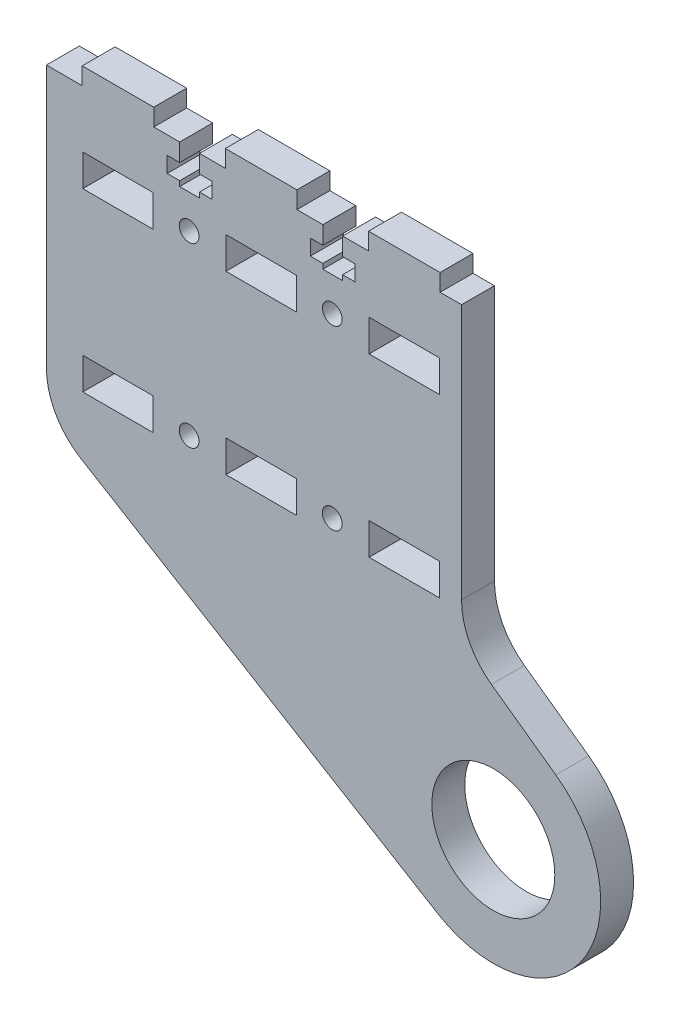
SolidWorks part; units mm, degrees
ref_plane "Front Plane" through (0, 0, 0) normal (0, 0, 1) x (1, 0, 0)
ref_plane "Top Plane" through (0, 0, 0) normal (0, 1, 0) x (1, 0, 0)
ref_plane "Right Plane" through (0, 0, 0) normal (1, 0, 0) x (0, 0, -1)
sketch "Sketch1" plane through (0, 0, 0) normal (0, 0, 1) x (1, 0, 0)
  line L0 (-38.0203, 0) -> (38.1796, 0) construction
  line L1 (31.7297, -12.8) -> (19.2297, -12.8)
  line L2 (38.1796, -12.8536) -> (38.1796, 12.8536)
  line L3 (31.7297, 12.8) -> (19.2297, 12.8)
  line L4 (-38.0203, -12.8) -> (-38.0203, 12.8)
  line L5 (38.1796, -12.8536) -> (-38.0203, 12.8) construction
  line L6 (38.1796, 12.8536) -> (-38.0203, -12.8) construction
  line L7 (6.3297, 18.442) -> (-6.1703, 18.442)
  line L8 (-19.0703, -18.442) -> (-31.5703, -12.8) construction
  line L9 (-19.0703, -12.8) -> (-31.5703, -18.442) construction
  line L10 (6.3297, -12.8) -> (-6.1703, -12.8)
  line L11 (-19.0703, -12.8) -> (-31.5703, -12.8)
  line L12 (31.7297, -12.8) -> (31.7297, -18.442)
  line L13 (19.2297, -12.8) -> (19.2297, -18.442)
  line L14 (38.1796, 28.575) -> (31.8297, 28.575)
  line L15 (-19.0703, 12.8) -> (-19.0703, 18.442)
  line L16 (-19.0703, 18.442) -> (-31.5703, 18.442)
  line L17 (-31.5703, 12.8) -> (-31.5703, 18.442)
  line L18 (-19.0703, 12.8) -> (-31.5703, 18.442) construction
  line L19 (-19.0703, 18.442) -> (-31.5703, 12.8) construction
  line L20 (-6.1703, 12.8) -> (-6.1703, 18.442)
  line L21 (6.3297, 12.8) -> (6.3297, 18.442)
  line L22 (31.7297, 18.442) -> (19.2297, 18.442)
  line L23 (19.2297, 12.8) -> (19.2297, 18.442)
  line L24 (31.7297, 12.8) -> (31.7297, 18.442)
  line L25 (-19.0703, 12.8) -> (-31.5703, 12.8)
  line L26 (6.3297, 12.8) -> (-6.1703, 12.8)
  line L27 (-38.0203, 12.8) -> (-38.0203, 28.575)
  line L28 (0.0797, 0) -> (0.0797, 28.575) construction
  line L29 (11.0271, 28.575) -> (6.4297, 28.575)
  line L30 (38.1796, 28.575) -> (38.1796, 12.8536)
  line L31 (31.7297, -18.442) -> (19.2297, -18.442)
  line L32 (6.3297, -12.8) -> (6.3297, -18.442)
  line L33 (-6.1703, -12.8) -> (-6.1703, -18.442)
  line L34 (-31.5703, -12.8) -> (-31.5703, -18.442)
  line L35 (-19.0703, -18.442) -> (-31.5703, -18.442)
  line L36 (-19.0703, -12.8) -> (-19.0703, -18.442)
  line L37 (6.3297, -18.442) -> (-6.1703, -18.442)
  line L38 (31.7297, -12.8) -> (19.2297, -12.8)
  line L39 (-19.0703, -12.8) -> (-31.5703, -12.8)
  line L40 (6.3297, -12.8) -> (-6.1703, -12.8)
  line L41 (6.3297, 12.8) -> (19.2297, 12.8) construction
  line L42 (-38.0203, -25.146) -> (31.4234, -67.1049)
  line L43 (38.1796, -25.146) -> (52.371, -35.3151)
  line L44 (-10.8677, 22.1694) -> (-14.3729, 22.1694) construction
  line L45 (-8.6516, 24.0109) -> (-16.5891, 24.0109) construction
  line L46 (-10.8677, 26.9875) -> (-14.3729, 26.9875) construction
  line L47 (-12.6203, 28.575) -> (-12.6203, 24.5335) construction
  line L48 (-6.1703, 12.8) -> (-19.0703, 12.8) construction
  line L49 (-14.3729, 21.717) -> (-14.3729, 22.6219)
  line L50 (12.7797, 0) -> (12.7797, 28.575) construction
  line L51 (14.5323, 25.4) -> (16.7484, 25.4)
  line L52 (14.5323, 22.6219) -> (16.7484, 22.6219)
  line L53 (11.0271, 25.4) -> (11.0271, 28.575)
  line L54 (-10.8677, 21.717) -> (-10.8677, 22.6219)
  line L55 (-38.0203, -12.8) -> (-38.0203, -25.146)
  line L56 (14.5323, 25.4) -> (14.5323, 28.575)
  line L57 (12.7797, 28.575) -> (12.7797, 24.5335) construction
  line L58 (38.1796, -12.8536) -> (38.1796, -25.146)
  line L59 (11.0271, 26.9875) -> (14.5323, 26.9875) construction
  line L60 (8.8109, 22.6219) -> (11.0271, 22.6219)
  line L61 (8.8109, 22.6219) -> (8.8109, 25.4)
  line L62 (8.8109, 25.4) -> (11.0271, 25.4)
  line L63 (16.7484, 22.6219) -> (16.7484, 25.4)
  line L64 (12.7797, 24.5335) -> (12.7797, 20.1202) construction
  line L65 (8.8109, 24.0109) -> (16.7484, 24.0109) construction
  line L66 (11.0271, 21.717) -> (14.5323, 21.717)
  line L67 (11.0271, 21.717) -> (11.0271, 22.6219)
  line L68 (-6.2703, 28.575) -> (-10.8677, 28.575)
  line L69 (14.5323, 21.717) -> (14.5323, 22.6219)
  line L70 (12.7797, 20.1202) -> (12.7797, 21.717) construction
  line L71 (11.0271, 22.1694) -> (14.5323, 22.1694) construction
  line L72 (-10.8677, 21.717) -> (-14.3729, 21.717)
  line L73 (-16.5891, 22.6219) -> (-16.5891, 25.4)
  line L74 (-8.6516, 25.4) -> (-10.8677, 25.4)
  line L75 (-8.6516, 22.6219) -> (-8.6516, 25.4)
  line L76 (-8.6516, 22.6219) -> (-10.8677, 22.6219)
  line L77 (-14.3729, 25.4) -> (-14.3729, 28.575)
  line L78 (-10.8677, 25.4) -> (-10.8677, 28.575)
  line L79 (-14.3729, 22.6219) -> (-16.5891, 22.6219)
  line L80 (-14.3729, 25.4) -> (-16.5891, 25.4)
  line L81 (-14.3729, 28.575) -> (-18.9703, 28.575)
  line L82 (19.1297, 31.623) -> (19.1297, 28.575)
  line L83 (-6.2703, 31.623) -> (6.4297, 31.623)
  line L84 (-6.2703, 31.623) -> (-6.2703, 28.575)
  line L85 (31.8297, 31.623) -> (31.8297, 28.575)
  line L86 (6.4297, 31.623) -> (6.4297, 28.575)
  line L87 (0.0797, 28.575) -> (0.0797, 31.623) construction
  line L88 (-6.2703, 30.099) -> (6.4297, 30.099) construction
  line L89 (31.8297, 30.099) -> (19.1297, 30.099) construction
  line L90 (31.8297, 31.623) -> (19.1297, 31.623)
  line L91 (19.1297, 28.575) -> (14.5323, 28.575)
  line L92 (-18.9703, 31.623) -> (-18.9703, 28.575)
  line L93 (-31.6703, 31.623) -> (-18.9703, 31.623)
  line L94 (-31.6703, 30.099) -> (-18.9703, 30.099) construction
  line L95 (-31.6703, 31.623) -> (-31.6703, 28.575)
  line L96 (-31.6703, 28.575) -> (-38.0203, 28.575)
  arc A0 (31.4234, -67.1049) -> (52.371, -35.3151) centre (41.275, -50.8) ccw
  circle A1 centre (12.7, 15.721) radius 1.7526
  circle A2 centre (-12.7, 15.721) radius 1.7526
  circle A3 centre (12.7, -15.721) radius 1.7526
  circle A4 centre (-12.7, -15.721) radius 1.7526
  circle A6 centre (41.275, -50.8) radius 10.9125
  point P0 (0, 0)
  point P8 (-25.3203, 15.621)
  point P16 (12.7, 30.1625)
  point P37 (-25.3203, -15.621)
  point P55 (12.7797, 26.9875)
  point P59 (12.7797, 24.0109)
  point P60 (-0.4211, 99.3522)
  point P62 (-25.6211, 23.1522)
  point P65 (12.7797, 22.1694)
  point P70 (-3.225, -28.575)
  point P73 (12.7797, 24.0109)
  point P91 (-12.6203, 24.0109)
  point P92 (-12.6203, 22.1694)
  point P97 (-12.6203, 26.9875)
  point P98 (-12.5407, 30.1625)
  point P99 (0.0797, 30.099)
  point P117 (25.4797, 30.099)
  point P120 (-25.3203, 30.099)
  dimension "D3" = 12.5
  dimension "D5" = 50.8
  dimension "D6" = 41.275
  dimension "D8" = 12.7
  dimension "D13" = 3.5052
  dimension "D11" = 28.575
  dimension "D19" = 21.825
  dimension "D7" = 38.1
  dimension "D1" = 25.6
  dimension "D2" = 76.2
  dimension "D4" = 5.642
  dimension "D9" = 12.7
  dimension "D10" = 3
  dimension "D12" = 2.921
  dimension "D14" = 2.921
  dimension "D15" = 15.721
  dimension "D16" = 12.7
  dimension "D17" = 3.048
  dimension "D20" = 9.525
  dimension "D21" = 9.525
  dimension "D18" = 12.7
  dimension "D22" = 3.5052
  dimension "D23" = 2.7781
  dimension "D24" = 7.9375
  dimension "D25" = 3.175
  dimension "D26" = 0.9049
extrude "Boss-Extrude1" add sketch "Sketch1" along normal blind 5.842 contours L58 L2 L30 L27 L4 L55 A4 L32 L37 L33 L10 L11 L36 L35 L34 L12 L31 L13 L1 L21 L26 L20 L7 L15 L25 L17 L16 L24 L3 L23 L22 region at (7.1677, -13.6845, 0)
fillet "Fillet1" [suppressed] radius 3.175
fillet "Fillet2" [suppressed] radius 3.175
fillet "Fillet3" [suppressed] radius 3.175
sketch "Sketch3" [suppressed] plane through (0, 0, 5.842) normal (0, 0, 1) x (1, 0, 0)
  line L0 (12.6, 94.996) -> (12.7, -15.721) construction
  circle A0 centre (12.7147, -32.004) radius 2.413
  dimension "D1" = 4.826
  dimension "D2" = 127
extrude "Cut-Extrude2" [suppressed] cut sketch "Sketch3" against normal through all
sketch "Sketch5" [suppressed] plane through (0, 0, 5.842) normal (0, 0, 1) x (1, 0, 0)
  line L1 (-55.0734, 111.0269) -> (34.825, 111.0269)
  line L2 (-55.0734, 111.0269) -> (-55.0734, 25.146)
  line L3 (-55.0734, 25.146) -> (34.825, 25.146)
  line L4 (34.825, 111.0269) -> (34.825, 25.146)
extrude "Cut-Extrude3" [suppressed] cut sketch "Sketch5" against normal through all
sketch "Sketch6" [suppressed] plane through (0, 0, 5.842) normal (0, 0, 1) x (1, 0, 0)
  line L0 (-34.925, 25.146) -> (-33.9441, 25.146) construction
  line L1 (31.4879, 25.146) -> (-22.4871, 25.146)
  line L2 (31.4879, 78.486) -> (34.6629, 74.676)
  line L3 (31.4879, 78.486) -> (-20.5821, 78.486)
  line L4 (-22.4871, 25.146) -> (-25.0279, 25.146)
  line L5 (34.6629, 25.146) -> (-22.4871, 78.486) construction
  line L6 (34.6629, 78.486) -> (-22.4871, 25.146) construction
  line L7 (6.0879, 25.146) -> (6.0879, 48.411) construction
  line L8 (-31.75, 25.146) -> (-22.4871, 51.816)
  line L9 (-38.1, -25.146) -> (-38.1, 25.4) construction
  line L10 (34.6629, 74.676) -> (34.6629, 41.021)
  line L11 (-31.75, 25.146) -> (-25.0279, 25.146)
  line L12 (-22.4871, 51.816) -> (-22.4871, 71.3764)
  line L13 (31.4879, 70.866) -> (31.4879, 42.926) construction
  line L14 (31.4879, 37.846) -> (31.4879, 25.146)
  line L15 (31.4879, 37.846) -> (34.6629, 41.021)
  circle A0 centre (31.4879, 70.866) radius 1.651
  circle A1 centre (31.4879, 42.926) radius 1.651
  circle A2 centre (-20.5821, 74.676) radius 1.651
  circle A3 centre (-19.3121, 27.686) radius 1.651
  arc A4 (-20.5821, 78.486) -> (-22.4871, 71.3764) centre (-20.5821, 74.676) ccw
  point P0 (6.0879, 51.816)
  point P13 (-25.7515, 23.0626)
  point P14 (-16.4886, 49.7326)
  dimension "D5" = 3.302
  dimension "D6" = 3.302
  dimension "D9" = 12.7
  dimension "D10" = 3.302
  dimension "D12" = 3.302
  dimension "D1" = 53.34
  dimension "D2" = 57.15
  dimension "D3" = 6.35
  dimension "D7" = 49.53
  dimension "D8" = 27.94
  dimension "D11" = 52.07
  dimension "D13" = 50.8
  dimension "D14" = 15.24
  dimension "D4" = 7.62
extrude "Boss-Extrude3" [suppressed] add sketch "Sketch6" against normal up to surface (5.842 mm away) up to face at (52.1875, -50.8, 0)
fillet "Fillet6" [suppressed] radius 3.175
fillet "Fillet7" [suppressed] radius 1.5875
sketch "Sketch7" [suppressed] plane through (0, 0, 5.842) normal (0, 0, 1) x (1, 0, 0)
  line L0 (20.9561, 53.086) -> (-41.1495, 53.086) construction
  line L2 (5.0811, 78.486) -> (5.0811, 25.1147) construction
  line L3 (30.7443, 78.486) -> (-20.5821, 78.486) construction
  line L4 (5.0811, 65.786) -> (5.0811, 40.386) construction
  line L5 (8.2561, 65.786) -> (8.2561, 40.386)
  line L6 (1.9061, 65.786) -> (1.9061, 40.386)
  line L7 (17.7811, 65.786) -> (17.7811, 40.386) construction
  line L8 (20.9561, 65.786) -> (20.9561, 40.386)
  line L9 (14.6061, 65.786) -> (14.6061, 40.386)
  line L10 (-24.5007, 53.086) -> (20.9561, 53.086) construction
  line L11 (-7.6189, 65.786) -> (-7.6189, 40.386) construction
  line L12 (-10.7939, 65.786) -> (-10.7939, 40.386)
  line L13 (-4.4439, 65.786) -> (-4.4439, 40.386)
  arc A0 (8.2561, 65.786) -> (1.9061, 65.786) centre (5.0811, 65.786) ccw
  arc A1 (1.9061, 40.386) -> (8.2561, 40.386) centre (5.0811, 40.386) ccw
  arc A2 (20.9561, 65.786) -> (14.6061, 65.786) centre (17.7811, 65.786) ccw
  arc A3 (14.6061, 40.386) -> (20.9561, 40.386) centre (17.7811, 40.386) ccw
  arc A4 (-10.7939, 65.786) -> (-4.4439, 65.786) centre (-7.6189, 65.786) cw
  arc A5 (-4.4439, 40.386) -> (-10.7939, 40.386) centre (-7.6189, 40.386) cw
  point P10 (5.0811, 53.086)
  point P18 (17.7811, 53.086)
  point P26 (-7.6189, 53.086)
  dimension "D2" = 3.175
  dimension "D1" = 25.4
  dimension "D3" = 25.4
  dimension "D4" = 2
extrude "Cut-Extrude4" [suppressed] cut sketch "Sketch7" against normal through all
sketch "Sketch9" [suppressed] plane through (0, 0, 5.842) normal (0, 0, 1) x (1, 0, 0)
  line L0 (-38.1, -7.52) -> (38.1, -7.52) construction
  line L1 (-38.1, -25.146) -> (-38.1, 21.971) construction
  line L2 (38.1, 21.971) -> (38.1, -25.146) construction
  line L3 (-19.15, 12.8) -> (-31.65, 12.8) construction
  text T0 "SERGE" font "Roboto Condensed" height in points 42
  dimension "D1" = 20.32
extrude "Cut-Extrude5" [suppressed] cut sketch "Sketch9" against normal blind 0.3969
sketch "Sketch10" [suppressed] plane through (0, 0, 5.842) normal (0, 0, 1) x (1, 0, 0)
  line L0 (-38.1, -4.345) -> (38.1, -4.345) construction
  line L1 (-38.1, -25.146) -> (-38.1, 21.971) construction
  line L2 (38.1, 21.971) -> (38.1, -25.146) construction
  line L3 (-19.15, 12.8) -> (-31.65, 12.8) construction
  text T0 "SERGE" font "Bebas Neue" height in points 36
  dimension "D1" = 17.145
extrude "Cut-Extrude6" [suppressed] cut sketch "Sketch10" against normal blind 0.1984
sketch "Sketch11" [suppressed] plane through (0, 0, 5.842) normal (0, 0, 1) x (1, 0, 0)
  line L0 (12.6, 94.996) -> (12.7, 15.721) construction
  line L1 (9.467, 61.7085) -> (15.817, 61.7085) construction
  line L2 (9.467, 63.296) -> (15.817, 63.296)
  line L3 (9.467, 60.121) -> (15.817, 60.121)
  line L4 (31.75, 55.3585) -> (-6.45, 55.3585) construction
  line L5 (-6.45, 61.4095) -> (-6.45, 28.321) construction
  line L6 (9.4508, 74.4085) -> (15.8008, 74.4085) construction
  line L7 (9.4508, 75.996) -> (15.8008, 75.996)
  line L8 (9.4508, 72.821) -> (15.8008, 72.821)
  line L9 (9.4345, 87.1085) -> (15.7845, 87.1085) construction
  line L10 (9.4345, 88.696) -> (15.7845, 88.696)
  line L11 (9.4345, 85.521) -> (15.7845, 85.521)
  line L12 (9.4345, 23.6085) -> (15.7845, 23.6085) construction
  line L13 (9.4345, 22.021) -> (15.7845, 22.021)
  line L14 (9.4345, 25.196) -> (15.7845, 25.196)
  line L15 (9.4508, 36.3085) -> (15.8008, 36.3085) construction
  line L16 (9.4508, 34.721) -> (15.8008, 34.721)
  line L17 (9.4508, 37.896) -> (15.8008, 37.896)
  line L18 (9.467, 49.0085) -> (15.817, 49.0085) construction
  line L19 (9.467, 47.421) -> (15.817, 47.421)
  line L20 (9.467, 50.596) -> (15.817, 50.596)
  arc A0 (9.467, 63.296) -> (9.467, 60.121) centre (9.467, 61.7085) ccw
  arc A1 (15.817, 60.121) -> (15.817, 63.296) centre (15.817, 61.7085) ccw
  arc A2 (9.4508, 75.996) -> (9.4508, 72.821) centre (9.4508, 74.4085) ccw
  arc A3 (15.8008, 72.821) -> (15.8008, 75.996) centre (15.8008, 74.4085) ccw
  arc A4 (9.4345, 88.696) -> (9.4345, 85.521) centre (9.4345, 87.1085) ccw
  arc A5 (15.7845, 85.521) -> (15.7845, 88.696) centre (15.7845, 87.1085) ccw
  arc A6 (9.4345, 22.021) -> (9.4345, 25.196) centre (9.4345, 23.6085) cw
  arc A7 (15.7845, 25.196) -> (15.7845, 22.021) centre (15.7845, 23.6085) cw
  arc A8 (9.4508, 34.721) -> (9.4508, 37.896) centre (9.4508, 36.3085) cw
  arc A9 (15.8008, 37.896) -> (15.8008, 34.721) centre (15.8008, 36.3085) cw
  arc A10 (9.467, 47.421) -> (9.467, 50.596) centre (9.467, 49.0085) cw
  arc A11 (15.817, 50.596) -> (15.817, 47.421) centre (15.817, 49.0085) cw
  point P6 (12.642, 61.7085)
  point P16 (12.65, 55.3585)
  point P19 (12.6258, 74.4085)
  point P26 (12.6095, 87.1085)
  point P32 (12.6095, 23.6085)
  point P39 (12.6258, 36.3085)
  point P46 (12.642, 49.0085)
  dimension "D1" = 1.5875
  dimension "D2" = 6.35
  dimension "D3" = 6.35
  dimension "D4" = 3
extrude "Cut-Extrude7" [suppressed] cut sketch "Sketch11" against normal through all
fillet "Fillet8" [suppressed] radius 25.4
fillet "Fillet10" radius 12.7 1 edges at (-38.0203, -25.146, 2.921)
fillet "Fillet11" radius 12.7 1 edges at (38.1796, -25.146, 2.921)
sketch "Sketch12" [suppressed] plane through (0, 0, 5.842) normal (0, 0, 1) x (1, 0, 0)
  line L1 (-59.2155, 110.7085) -> (34.825, 110.7085)
  line L2 (-59.2155, 110.7085) -> (-59.2155, 25.146)
  line L3 (-59.2155, 25.146) -> (34.825, 25.146)
  line L4 (34.825, 110.7085) -> (34.825, 25.146)
  line L5 (-59.2155, 110.7085) -> (34.825, 25.146) construction
  line L6 (-59.2155, 25.146) -> (34.825, 110.7085) construction
  arc A0 (31.65, 28.321) -> (34.825, 25.146) centre (34.825, 28.321) ccw construction
  point P4 (-12.1952, 67.9272)
sketch "Sketch16" plane through (0, 0, 0) normal (0, 0, -1) x (-1, 0, 0)
  line L0 (-35.6396, 28.575) -> (-35.6396, -23.3259)
  line L1 (-38.1796, 28.575) -> (-31.8297, 28.575) construction
  line L2 (-35.6396, -23.3259) -> (-43.4823, -28.9457)
  line L3 (-43.4823, -28.9457) -> (-52.371, -35.3151) construction
  line L4 (-38.1796, 28.575) -> (-38.1796, -18.6225) construction
  line L5 (-38.1796, 28.575) -> (-35.6396, 28.575)
  line L6 (-38.1796, 28.575) -> (-38.1796, -18.6225)
  arc A0 (-43.4823, -28.9457) -> (-38.1796, -18.6225) centre (-50.8796, -18.6225) ccw construction
  arc A1 (-43.4823, -28.9457) -> (-38.1796, -18.6225) centre (-50.8796, -18.6225) ccw
  dimension "D1" = 2.54
extrude "Cut-Extrude9" cut sketch "Sketch16" against normal through all
fillet "Fillet12" radius 12.7 1 edges at (35.6396, -23.3259, 2.921)
